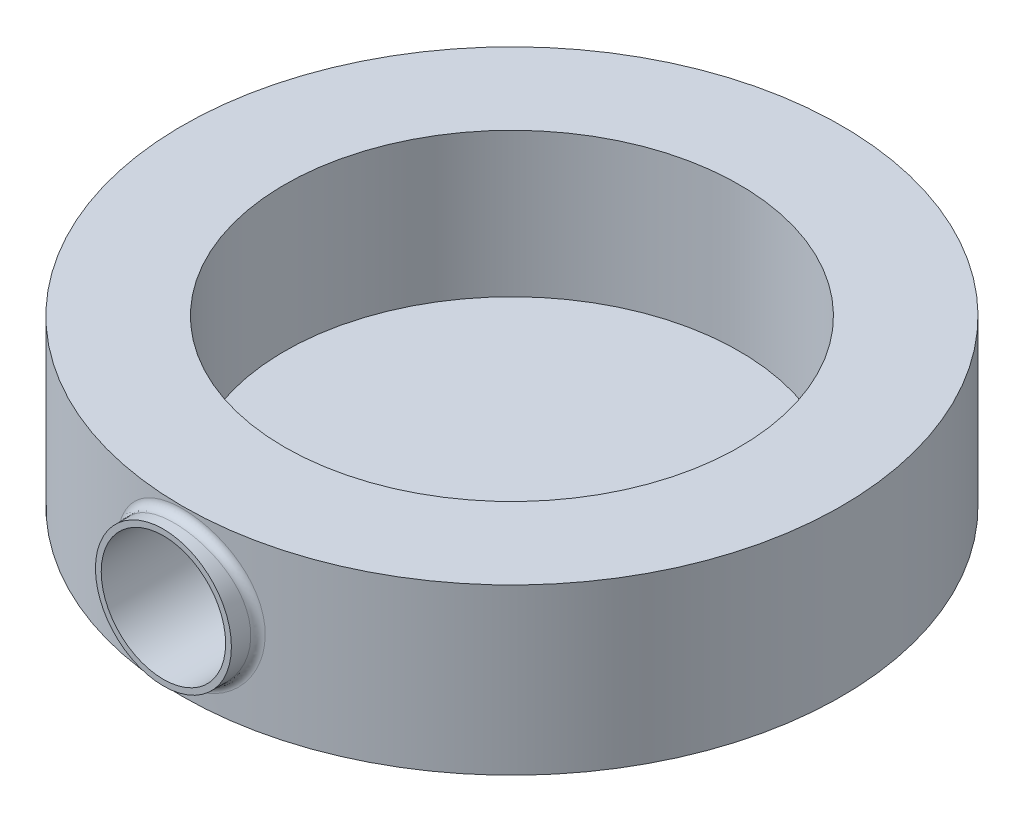
SolidWorks part; units mm, degrees
ref_plane "Front Plane" through (0, 0, 0) normal (0, 0, 1) x (1, 0, 0)
ref_plane "Top Plane" through (0, 0, 0) normal (0, 1, 0) x (1, 0, 0)
ref_plane "Right Plane" through (0, 0, 0) normal (1, 0, 0) x (0, 0, -1)
sketch "Sketch1" plane through (0, 0, 0) normal (0, 1, 0) x (1, 0, 0)
  circle A0 centre (0, 0) radius 400
  dimension "D1" = 800
extrude "Boss-Extrude1" add sketch "Sketch1" along normal blind 200
ref_plane "Plane1" through (0, 0, 400) normal (0, 0, 1) x (1, 0, 0)
sketch "Sketch2" plane through (0, 0, 400) normal (0, 0, 1) x (1, 0, 0)
  circle A0 centre (0, 104.9334) radius 75.5
  circle A2 centre (0, 104.9334) radius 82.5
  dimension "D1" = 151
  dimension "D2" = 165
extrude "Boss-Extrude2" add sketch "Sketch2" along normal blind 33 from offset 10 offset against normal yes
extrude "Cut-Extrude1" cut sketch "Sketch2<2>" against normal blind 432 contours A0 region at (0, 104.9334, 400)
sketch "Sketch2<2>" plane through (0, 0, 400) normal (0, 0, 1) x (1, 0, 0) same geometry as "Sketch2"
sketch "Sketch3" plane through (0, 200, 0) normal (0, 1, 0) x (1, 0, 0)
  circle A0 centre (0, 0) radius 275.9588
extrude "Cut-Extrude3" cut sketch "Sketch3" against normal blind 175
ref_plane "Plane2" through (0, 0, 380) normal (0, 0, 1) x (1, 0, 0)
fillet "Fillet2" radius 10 1 edges at (80.7217, 121.9702, 391.7703) type face fillet first side face at (82.5, 104.9334, 423) second side face at (0, 0, 400)
equation "\"base\" = 80cm"
equation "\"D1@Sketch1\"=\"base\""
equation "\"height\"= 20cm"
equation "\"D1@Boss-Extrude1\"=\"height\""
